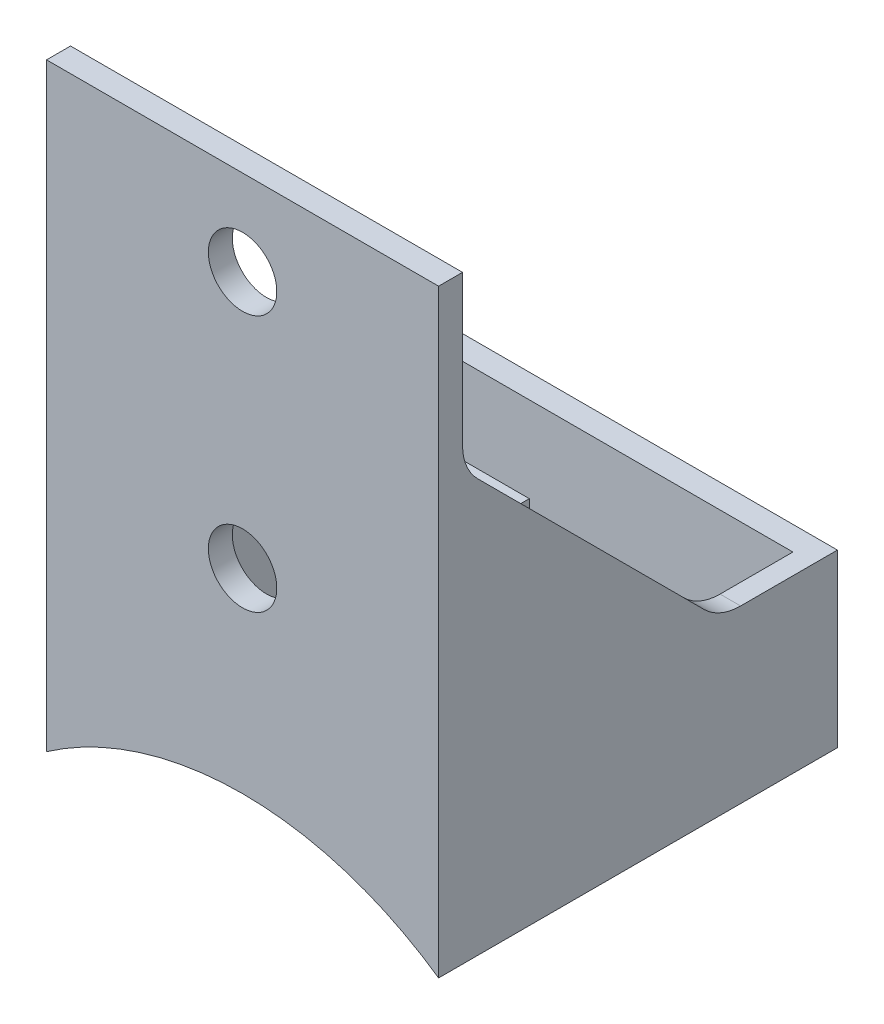
SolidWorks part; units mm, degrees
ref_plane "前视基准面" through (0, 0, 0) normal (0, 0, 1) x (1, 0, 0)
ref_plane "上视基准面" through (0, 0, 0) normal (0, 1, 0) x (1, 0, 0)
ref_plane "右视基准面" through (0, 0, 0) normal (1, 0, 0) x (0, 0, -1)
sketch "草图1" plane through (0, 0, 0) normal (0, 1, 0) x (1, 0, 0)
  line L0 (0, -1000) -> (0, 49000) construction
  line L1 (-10.25, 10.25) -> (10.25, 10.25)
  line L2 (-10.25, 10.25) -> (-10.25, -10.25)
  line L3 (-10.25, -10.25) -> (10.25, -10.25)
  line L4 (10.25, 10.25) -> (10.25, -10.25)
  line L5 (-10.25, 10.25) -> (10.25, -10.25) construction
  line L6 (-10.25, -10.25) -> (10.25, 10.25) construction
  line L7 (-5.15, 7.65) -> (-5.15, 10.25)
  line L8 (-11.45, 11.65) -> (11.45, 11.65)
  line L9 (-11.45, 11.65) -> (-11.45, -11.65)
  line L10 (-11.45, -11.65) -> (11.45, -11.65)
  line L11 (11.45, 11.65) -> (11.45, -11.65)
  line L12 (-11.45, 11.65) -> (11.45, -11.65) construction
  line L13 (-11.45, -11.65) -> (11.45, 11.65) construction
  line L14 (-7.62, 5.18) -> (-10.25, 5.18)
  line L15 (5.15, 7.65) -> (5.15, 10.25)
  line L16 (-10.25, 10.25) -> (-10.25, -10.25)
  line L17 (10.25, 10.25) -> (10.25, -10.25)
  line L18 (7.62, 5.18) -> (10.25, 5.18)
  line L19 (-10.25, -10.25) -> (-11.45, -10.25)
  line L20 (10.25, -10.25) -> (11.45, -10.25)
  circle A1 centre (-7.62, 7.65) radius 1.27
  arc A3 (-7.62, 5.18) -> (-5.15, 7.65) centre (-7.62, 7.65) ccw
  arc A4 (-5.15, 7.65) -> (-9.3815, 9.3815) centre (-7.62, 7.65) ccw construction
  arc A5 (-9.3815, 9.3815) -> (-7.62, 5.18) centre (-7.62, 7.65) ccw construction
  arc A6 (7.62, 5.18) -> (5.15, 7.65) centre (7.62, 7.65) cw
  circle A7 centre (7.62, 7.65) radius 1.27
  arc A8 (9.3815, 9.3815) -> (7.62, 5.18) centre (7.62, 7.65) cw construction
  arc A9 (5.15, 7.65) -> (9.3815, 9.3815) centre (7.62, 7.65) cw construction
  point P0 (0, 0)
  point P12 (0, 0)
  dimension "D3" = 2.54
  dimension "D4" = 15.24
  dimension "D5" = 2.6
  dimension "D8" = 1.2
  dimension "D1" = 20.5
  dimension "D2" = 20.5
  dimension "D6" = 1.4
  dimension "D7" = 1.2
extrude "凸台-拉伸1" add sketch "草图1" along normal blind 10 contours L11 L8 L9 L10 L1 L4 L17 L3 L2 | L20 L3 L19 L9 L10 L11 region at (-10.5669, 0, -7.715) region at (0, 0, 10.95)
extrude "凸台-拉伸2" add sketch "草图1<4>" along normal blind 5 contours L14 A3 L7 L1 L2 A1 | A6 L18 L4 L1 L15 A7 region at (-7.7, 0, -10.1781) region at (7.7, 0, -10.1781)
sketch "草图1<4>" plane through (0, 0, 0) normal (0, 1, 0) x (1, 0, 0) same geometry as "草图1"
extrude "凸台-拉伸3" add sketch "草图1<5>" along normal blind 10 contours L20 L3 L19 L9 L10 L11 region at (0, 0, 10.95)
sketch "草图1<5>" plane through (0, 0, 0) normal (0, 1, 0) x (1, 0, 0) same geometry as "草图1"
sketch "草图3" plane through (0, 10, 0) normal (0, 1, 0) x (1, 0, 0)
  line L0 (-11.45, 11.65) -> (-11.45, -11.65) construction
  line L1 (-11.45, -10.25) -> (11.45, -10.25)
  line L2 (-11.45, -10.25) -> (-11.45, -11.65)
  line L3 (-11.45, -11.65) -> (11.45, -11.65)
  line L4 (11.45, -10.25) -> (11.45, -11.65)
extrude "凸台-拉伸4" add sketch "草图3" along normal blind 25
sketch "草图4" plane through (0, 0, -11.65) normal (0, 0, -1) x (-1, 0, 0)
  circle A0 centre (0, -16.3981) radius 20
  dimension "D1" = 40
extrude "切除-拉伸1" cut sketch "草图4" against normal up to next
sketch "草图5" plane through (0, 0, 10.25) normal (0, 0, -1) x (-1, 0, 0)
  line L1 (-11.45, 35) -> (11.45, 35) construction
  circle A0 centre (0, 15) radius 2
  circle A1 centre (0, 30) radius 2
  point P9 (0, 35)
  dimension "D1" = 4
  dimension "D2" = 4
  dimension "D4" = 15
  dimension "D3" = 5
extrude "切除-拉伸2" cut sketch "草图5" against normal through all
chamfer "倒角1" distance 15 angle 45 2 edges at (10.85, 10, 10.25) (-10.85, 10, 10.25)
fillet "圆角1" radius 3 4 edges at (10.85, 10, -4.75) (10.85, 25, 10.25) (-10.85, 25, 10.25) (-10.85, 10, -4.75)
